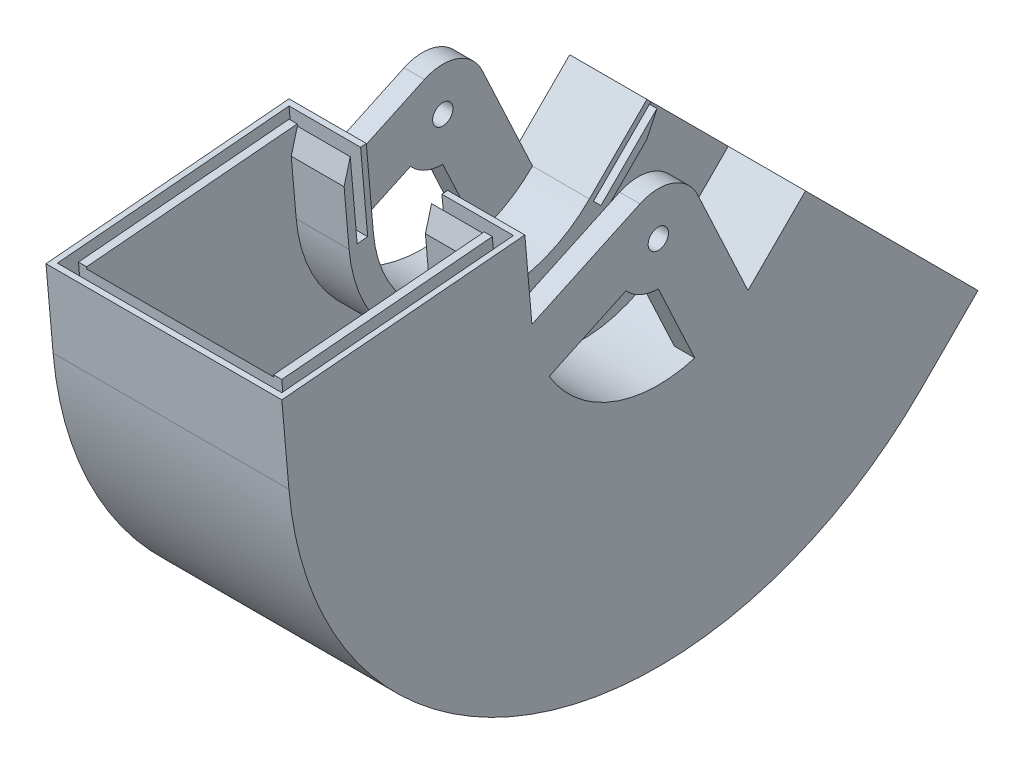
SolidWorks part; units mm, degrees
ref_plane "Front Plane" through (0, 0, 0) normal (0, 0, 1) x (1, 0, 0)
ref_plane "Top Plane" through (0, 0, 0) normal (0, 1, 0) x (1, 0, 0)
ref_plane "Right Plane" through (0, 0, 0) normal (1, 0, 0) x (0, 0, -1)
sketch "Sketch3" plane through (0, 0, 0) normal (1, 0, 0) x (0, 0, -1)
  line L0 (-39.4732, -3.4535) -> (-107.7923, -9.4306)
  line L1 (28.0184, -28.0184) -> (76.5118, -76.5118)
  line L2 (-39.4732, -3.4535) -> (0, 0) construction
  line L3 (0, 0) -> (28.0184, -28.0184) construction
  line L4 (0, 55) -> (0, -55) construction
  line L5 (-107.7923, -9.4306) -> (-115.3833, -10.0947)
  line L6 (76.5118, -76.5118) -> (81.8999, -81.8999)
  arc A2 (-107.7923, -9.4306) -> (76.5118, -76.5118) centre (0, 0) ccw
  arc A4 (-47.0642, -4.1176) -> (33.4066, -33.4066) centre (0, 0) ccw
  arc A5 (-39.4732, -3.4535) -> (28.0184, -28.0184) centre (0, 0) ccw
  arc A6 (-115.3833, -10.0947) -> (81.8999, -81.8999) centre (0, 0) ccw
  dimension "D1" = 216.408
  dimension "D2" = 135
  dimension "D3" = 94.488
  dimension "D4" = 7.62
  dimension "D6" = 7.62
  dimension "D5" = 130
extrude "Boss-Extrude2" add sketch "Sketch3" along normal blind 58.42 contours L5 A6 L6 A2 | A5 L0 A4 L1 region at (0, -38.0953, 13.8655) region at (0, -103.7848, 37.7746)
sketch "Sketch4" plane through (58.42, 0, 0) normal (1, 0, 0) x (0, 0, -1)
  line L0 (-115.3833, -10.0947) -> (-39.4732, -3.4535)
  line L1 (28.0184, -28.0184) -> (81.8999, -81.8999)
  arc A0 (-39.4732, -3.4535) -> (28.0184, -28.0184) centre (0, 0) ccw
  arc A1 (-39.4732, -3.4535) -> (28.0184, -28.0184) centre (0, 0) ccw construction
  arc A2 (-115.3833, -10.0947) -> (81.8999, -81.8999) centre (0, 0) ccw
  arc A3 (-115.3833, -10.0947) -> (81.8999, -81.8999) centre (0, 0) ccw construction
  arc M1 (28.0184, -28.0184) -> (-39.4732, -3.4535) centre (0, 0) cw
  line M2 (-39.4732, -3.4535) -> (-47.0642, -4.1176)
  arc M3 (-47.0642, -4.1176) -> (33.4066, -33.4066) centre (0, 0) ccw
  line M4 (33.4066, -33.4066) -> (28.0184, -28.0184)
extrude "Boss-Extrude3" add sketch "Sketch4" along normal blind 7.62 contours L0 A2 L1 M3 | M4 M1 M2 M3 region at (58.42, -64.8169, 23.5914) region at (58.42, -4.6982, 43.1889)
ref_plane "Midplane" through (29.21, 0, 0) normal (-1, 0, 0) x (0, 0, 1)
mirror "Mirror1" about plane through (29.21, 0, 0) normal (-1, 0, 0) of "Boss-Extrude3"
sketch "Sketch6" plane through (0, 0, 0) normal (0, 0.9962, 0.0872) x (1, 0, 0)
  line L27 (-5.842, -41.402) -> (64.262, -41.402)
  line L28 (-5.842, -41.402) -> (-5.842, -114.046)
  line L29 (-5.842, -114.046) -> (64.262, -114.046)
  line L30 (64.262, -41.402) -> (64.262, -114.046)
  line L31 (-2.54, -44.704) -> (60.96, -44.704)
  line L32 (-2.54, -44.704) -> (-2.54, -110.744)
  line L33 (-2.54, -110.744) -> (60.96, -110.744)
  line L34 (60.96, -44.704) -> (60.96, -110.744)
  line L35 (58.42, -47.244) -> (0, -47.244) construction
  line L36 (0, -108.204) -> (0, 69.5522) construction
  line L37 (58.42, 69.5522) -> (58.42, -108.204) construction
  line L38 (58.42, -108.204) -> (0, -108.204) construction
  line L40 (0, -47.244) -> (58.42, -47.244)
  line L41 (0, -47.244) -> (0, -108.204)
  line L42 (0, -108.204) -> (58.42, -108.204)
  line L43 (58.42, -47.244) -> (58.42, -108.204)
  line L44 (-7.62, -39.624) -> (66.04, -39.624)
  line L45 (-7.62, -39.624) -> (-7.62, -115.824)
  line L46 (-7.62, -115.824) -> (66.04, -115.824)
  line L47 (66.04, -39.624) -> (66.04, -115.824)
  line M21 (-7.62, -39.624) -> (-7.62, -115.824)
  line M22 (-7.62, -115.824) -> (66.04, -115.824)
  line M23 (66.04, -115.824) -> (66.04, -39.624)
  line M24 (66.04, -39.624) -> (-7.62, -39.624)
  line M25 (58.42, -108.204) -> (0, -108.204)
  line M26 (0, -108.204) -> (0, -47.244)
  line M27 (0, -47.244) -> (58.42, -47.244)
  line M28 (58.42, -47.244) -> (58.42, -108.204)
  dimension "D1" = 3.302
  dimension "D2" = 3.302
  dimension "D3" = 3.302
  dimension "D4" = 3.302
  dimension "D5" = 2.54
  dimension "D6" = 2.54
  dimension "D7" = 2.54
  dimension "D8" = 2.54
extrude "Boss-Extrude4" add sketch "Sketch6" along normal blind 25.4 contours L27 L30 L29 L28 M24 M21 M22 M23 | L34 L31 L32 L33 M28 M25 M26 M27 region at (29.21, -3.9761, 45.4466) region at (29.21, -3.5458, 40.529)
sketch "Sketch7" plane through (0, 0, 0) normal (0, 0.7071, -0.7071) x (1, 0, 0)
  line L0 (-5.842, 114.046) -> (64.262, 114.046)
  line L1 (-5.842, 114.046) -> (-5.842, 41.402)
  line L2 (-5.842, 41.402) -> (64.262, 41.402)
  line L3 (64.262, 114.046) -> (64.262, 41.402)
  line L4 (-2.54, 110.744) -> (60.96, 110.744)
  line L5 (-2.54, 110.744) -> (-2.54, 44.704)
  line L6 (-2.54, 44.704) -> (60.96, 44.704)
  line L7 (60.96, 110.744) -> (60.96, 44.704)
  line L8 (0, 108.204) -> (58.42, 108.204)
  line L9 (0, 108.204) -> (0, 47.244)
  line L10 (0, 47.244) -> (58.42, 47.244)
  line L11 (58.42, 108.204) -> (58.42, 47.244)
  line L12 (-7.62, 115.824) -> (66.04, 115.824)
  line L13 (-7.62, 115.824) -> (-7.62, 39.624)
  line L14 (-7.62, 39.624) -> (66.04, 39.624)
  line L15 (66.04, 115.824) -> (66.04, 39.624)
  line L16 (58.42, 108.204) -> (0, 108.204) construction
  line L17 (58.42, 47.244) -> (58.42, 108.204) construction
  line L18 (66.04, 115.824) -> (-7.62, 115.824) construction
  line L19 (66.04, 39.624) -> (66.04, 115.824) construction
  line L20 (-7.62, 39.624) -> (-7.62, 115.824) construction
  line L21 (66.04, 39.624) -> (-7.62, 39.624) construction
  point P26 (0, 47.244)
  point P28 (66.04, 39.624)
  line M17 (66.04, 115.824) -> (-7.62, 115.824)
  line M18 (-7.62, 115.824) -> (-7.62, 39.624)
  line M19 (-7.62, 39.624) -> (66.04, 39.624)
  line M20 (66.04, 39.624) -> (66.04, 115.824)
  line M21 (0, 47.244) -> (0, 108.204)
  line M22 (0, 108.204) -> (58.42, 108.204)
  line M23 (58.42, 108.204) -> (58.42, 47.244)
  line M24 (58.42, 47.244) -> (0, 47.244)
  dimension "D1" = 3.302
  dimension "D2" = 3.302
  dimension "D3" = 3.302
  dimension "D4" = 3.302
  dimension "D5" = 2.54
  dimension "D6" = 2.54
  dimension "D7" = 2.54
  dimension "D8" = 2.54
extrude "Boss-Extrude5" add sketch "Sketch7" along normal blind 25.4 contours L0 L3 L2 L1 M20 M17 M18 M19 | L7 L4 L5 L6 M24 M21 M22 M23 region at (29.21, -77.66, -77.66) region at (29.21, -81.1505, -81.1505)
chamfer "Chamfer1" distance 7.62 angle 20 4 edges at (29.21, 15.8727, 110.006) (29.21, 21.1858, 49.278) (29.21, -58.5513, -94.4723) (29.21, -15.446, -51.3671) first distance on face at (29.21, 3.2211, 108.8991) first distance on face at (29.21, 8.5341, 48.1711) first distance on face at (29.21, -67.5315, -85.492) first distance on face at (29.21, -24.4263, -42.3868)
ref_plane "Plane2" through (0, 5.896, -2.146) normal (0, -0.9397, 0.342) x (-1, 0, 0)
sketch "Sketch10" plane through (0, 5.896, -2.146) normal (0, -0.9397, 0.342) x (-1, 0, 0)
  line L0 (-66.04, 115.7067) -> (7.62, 115.7067) construction
  line L1 (-16.51, 95.5358) -> (-41.91, 95.5358)
  line L2 (-16.51, 95.5358) -> (-16.51, -82.1857)
  line L3 (-16.51, -82.1857) -> (-41.91, -82.1857)
  line L4 (-41.91, 95.5358) -> (-41.91, -82.1857)
  point P4 (-29.21, 115.7067)
  point P5 (-29.21, 95.5358)
  point P8 (0, 0)
  dimension "D1" = 25.4
extrude "Cut-Extrude3" cut sketch "Sketch10" along normal up to next
sketch "Sketch11" plane through (-7.62, 0, 0) normal (-1, 0, 0) x (0, 0, 1)
  line L0 (-12.2825, 5.7274) -> (-28.0184, -28.0184)
  line L1 (-45.9789, -10.0579) -> (-28.0184, -28.0184) construction
  line L2 (5.7274, 12.2825) -> (39.4732, -3.4535)
  line L3 (41.687, 21.8499) -> (39.4732, -3.4535) construction
  line L4 (0, -13.5522) -> (-11.3792, -37.9549)
  line L5 (10.0937, -9.0432) -> (34.0735, -20.2252)
  arc A0 (0, -13.5522) -> (10.0937, -9.0432) centre (0, 0) ccw
  arc A1 (-28.0184, -28.0184) -> (39.4732, -3.4535) centre (0, 0) ccw construction
  arc A2 (-28.0184, -28.0184) -> (-11.3792, -37.9549) centre (0, 0) ccw
  circle A3 centre (0, 0) radius 3.175
  arc A4 (5.7274, 12.2825) -> (-12.2825, 5.7274) centre (0, 0) ccw
  arc A5 (34.0735, -20.2252) -> (39.4732, -3.4535) centre (0, 0) ccw
  dimension "D3" = 6.35
  dimension "D1" = 90
  dimension "D2" = 17.4823
extrude "Boss-Extrude6" add sketch "Sketch11" against normal blind 6.35
mirror "Mirror2" about plane through (29.21, 0, 0) normal (-1, 0, 0) of "Boss-Extrude6"
